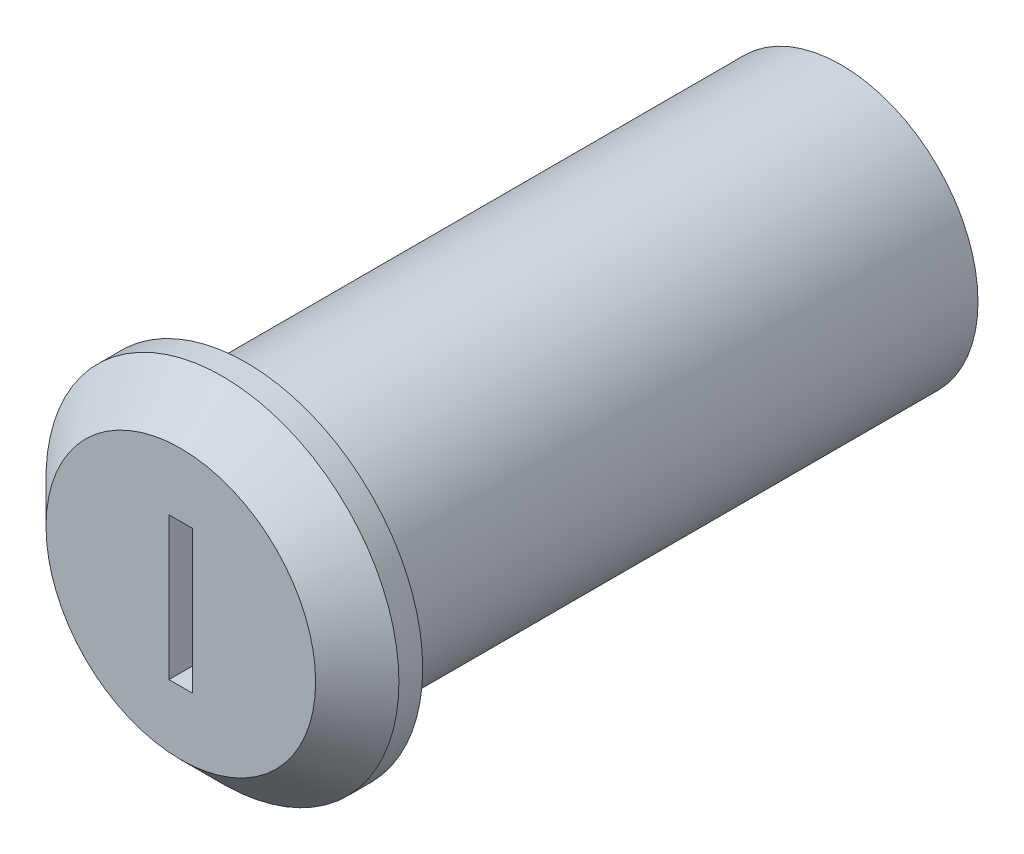
SolidWorks part; units mm, degrees
ref_plane "Front" through (0, 0, 0) normal (0, 0, 1) x (1, 0, 0)
ref_plane "Top" through (0, 0, 0) normal (0, 1, 0) x (1, 0, 0)
ref_plane "Right" through (0, 0, 0) normal (1, 0, 0) x (0, 0, -1)
sketch "Sketch1" plane through (0, 0, 0) normal (0, 0, 1) x (1, 0, 0)
  circle A0 centre (0, 0) radius 5.75
  dimension "D1" = 11.5
extrude "Boss-Extrude1" add sketch "Sketch1" against normal blind 25
sketch "Sketch2" plane through (0, 0, 0) normal (0, 0, 1) x (1, 0, 0)
  circle A0 centre (0, 0) radius 7.415
  dimension "D1" = 14.83
extrude "Boss-Extrude2" add sketch "Sketch2" along normal blind 1
sketch "Sketch3" plane through (0, 0, 1) normal (0, 0, 1) x (1, 0, 0)
  circle A1 centre (0, 0) radius 7.415
  circle A2 centre (0, 0) radius 7.415
  dimension "D1" = 0
extrude "Boss-Extrude3" add sketch "Sketch3" along normal blind 1.75 draft 45
sketch "Sketch4" plane through (0, 0, 2.75) normal (0, 0, 1) x (1, 0, 0)
  line L1 (-0.5, -3) -> (0.5, -3)
  line L2 (-0.5, -3) -> (-0.5, 3)
  line L3 (-0.5, 3) -> (0.5, 3)
  line L4 (0.5, -3) -> (0.5, 3)
  line L5 (-0.5, -3) -> (0.5, 3) construction
  line L6 (-0.5, 3) -> (0.5, -3) construction
  point P0 (0, 0)
  dimension "D1" = 1
  dimension "D2" = 6
extrude "Cut-Extrude1" cut sketch "Sketch4" against normal blind 1
sketch "Panel Cut Guide" plane through (0, 0, 0) normal (0, 0, 1) x (1, 0, 0)
  line L0 (0, 5.775) -> (0, 0) construction
  line L1 (-5.325, 2.2349) -> (-5.325, -2.2349)
  line L2 (5.325, 2.2349) -> (5.325, -2.2349)
  circle A0 centre (0, 0) radius 5.775 construction
  arc A1 (-5.325, 2.2349) -> (5.325, 2.2349) centre (0, 0) cw
  arc A2 (5.325, -2.2349) -> (-5.325, -2.2349) centre (0, 0) cw
  point P9 (5.3072, 2.2768)
  point P10 (-5.3212, -2.2441)
  dimension "D1" = 11.55
  dimension "D2" = 10.65
